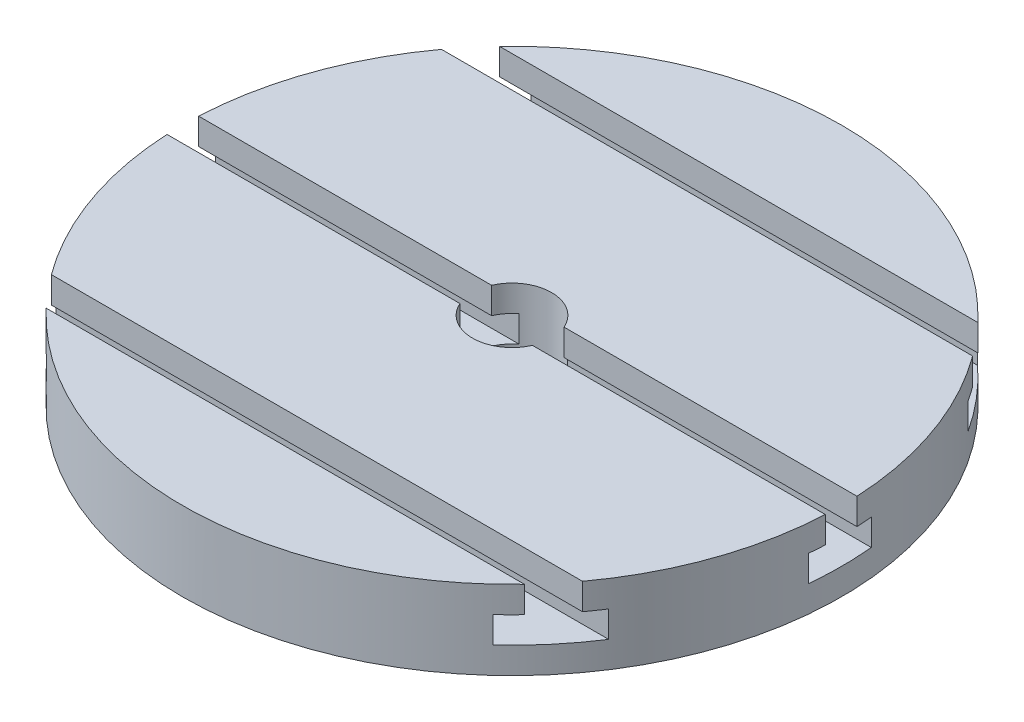
SolidWorks part; units mm, degrees
ref_plane "Спереди" through (0, 0, 0) normal (0, 0, 1) x (1, 0, 0)
ref_plane "Сверху" through (0, 0, 0) normal (0, 1, 0) x (1, 0, 0)
ref_plane "Справа" through (0, 0, 0) normal (1, 0, 0) x (0, 0, -1)
sketch "Эскиз1" plane through (0, 0, 0) normal (1, 0, 0) x (0, 0, -1)
  line L0 (0, -12.6281) -> (0, 29.9138) construction
  line L1 (15, 0) -> (125, 0)
  line L2 (15, 0) -> (15, 30)
  line L3 (15, 30) -> (125, 30)
  line L4 (125, 0) -> (125, 30)
revolve "Повернуть1" add sketch "Эскиз1" angle 360 about L0
sketch "Эскиз2" plane through (0, 0, 0) normal (1, 0, 0) x (0, 0, -1)
  line L1 (11.8734, 10) -> (11.8734, 20)
  line L2 (11.8734, 20) -> (6, 20)
  line L3 (6, 20) -> (6, 30)
  line L4 (125, 30) -> (-125, 30) construction
  line L5 (6, 30) -> (-6, 30)
  line L6 (15, 30) -> (-15, 30) construction
  line L10 (0, 28.7888) -> (0, -3.461) construction
  line L11 (-6, 20) -> (-6, 30)
  line L12 (-11.8734, 20) -> (-6, 20)
  line L13 (-11.8734, 10) -> (-11.8734, 20)
  line L14 (-11.8734, 10) -> (11.8734, 10)
  line L15 (68.1266, 10) -> (91.8734, 10)
  line L16 (91.8734, 10) -> (91.8734, 20)
  line L17 (91.8734, 20) -> (86, 20)
  line L18 (86, 20) -> (86, 30)
  line L19 (86, 30) -> (74, 30)
  line L20 (74, 20) -> (74, 30)
  line L21 (68.1266, 20) -> (74, 20)
  line L22 (68.1266, 10) -> (68.1266, 20)
  line L24 (-91.8734, 10) -> (-68.1266, 10)
  line L25 (-68.1266, 10) -> (-68.1266, 20)
  line L26 (-68.1266, 20) -> (-74, 20)
  line L27 (-74, 20) -> (-74, 30)
  line L28 (-74, 30) -> (-86, 30)
  line L29 (-86, 20) -> (-86, 30)
  line L30 (-91.8734, 20) -> (-86, 20)
  line L31 (-91.8734, 10) -> (-91.8734, 20)
  point P12 (0, 30)
  point P26 (80, 30)
  point P37 (-80, 30)
  dimension "D1" = 6
  dimension "D3" = 10
  dimension "D4" = 10
  dimension "D5" = 2
  dimension "D6" = 2
extrude "Вырез-Вытянуть1" cut sketch "Эскиз2" against normal mid plane 300
